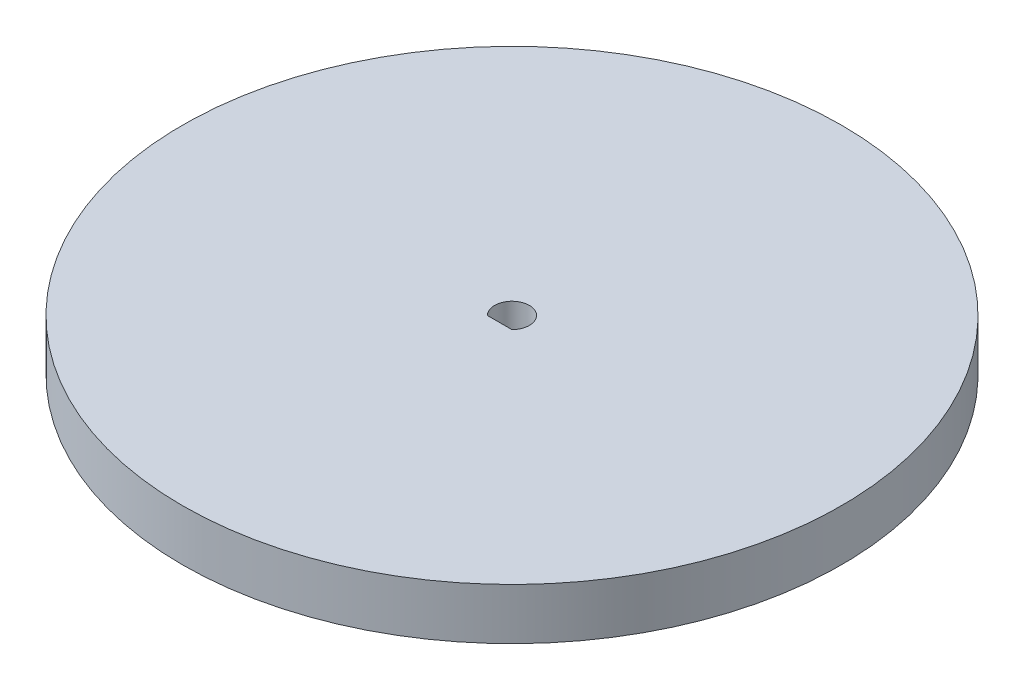
SolidWorks part; units mm, degrees
ref_plane "Front Plane" through (0, 0, 0) normal (0, 0, 1) x (1, 0, 0)
ref_plane "Top Plane" through (0, 0, 0) normal (0, 1, 0) x (1, 0, 0)
ref_plane "Right Plane" through (0, 0, 0) normal (1, 0, 0) x (0, 0, -1)
sketch "Sketch1" plane through (0, 0, 0) normal (0, 1, 0) x (1, 0, 0)
  line L0 (-15.8528, -2.1977) -> (-12.5138, -2.1977)
  arc A1 (-15.8528, -2.1977) -> (-12.5138, -2.1977) centre (-14.1833, -0.5085) cw
  circle A2 centre (-14.1833, -0.5085) radius 45
  dimension "D2" = 2.375
  dimension "D3" = 90
  dimension "D1" = 3.339
extrude "Boss-Extrude1" add sketch "Sketch1" along normal blind 7
